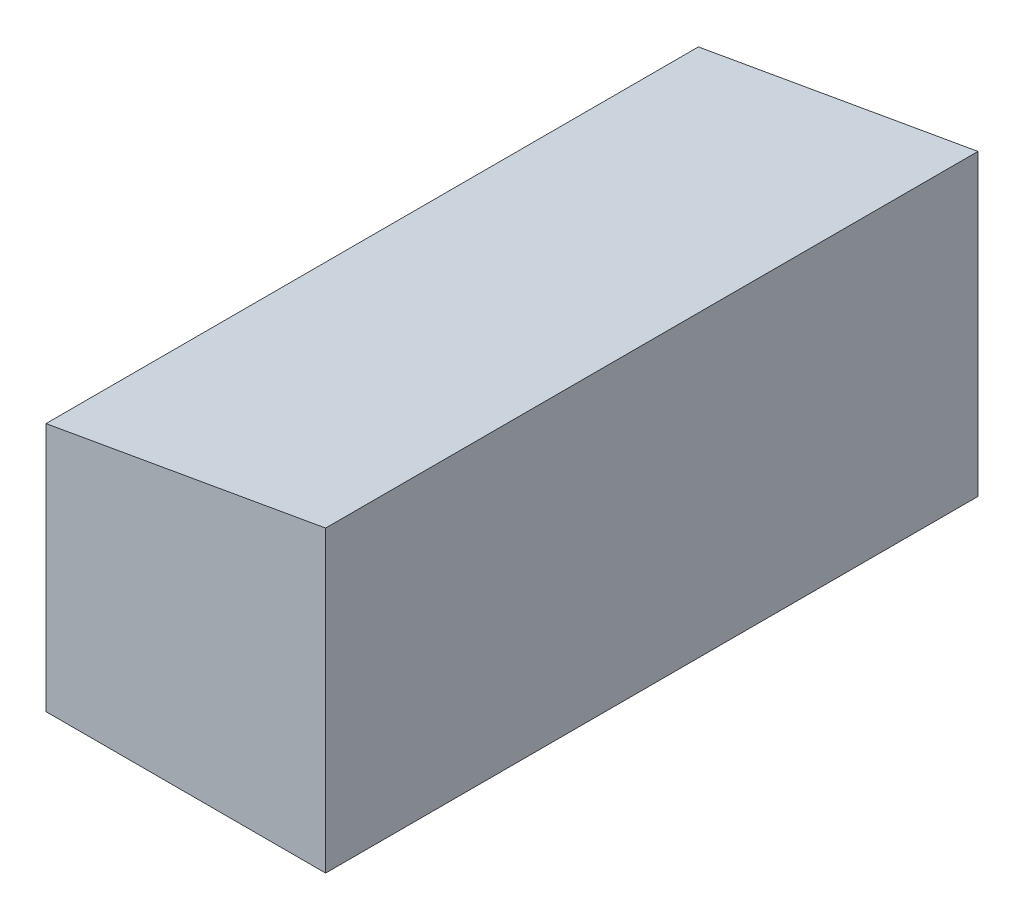
SolidWorks part; units mm, degrees
material "SPF Select 2Btr Grade Lumber"
ref_plane "Front Plane" through (0, 0, 0) normal (0, 0, 1) x (1, 0, 0)
ref_plane "Top Plane" through (0, 0, 0) normal (0, 1, 0) x (1, 0, 0)
ref_plane "Right Plane" through (0, 0, 0) normal (1, 0, 0) x (0, 0, -1)
sketch "Sketch1" plane through (0, 0, 0) normal (0, 0, 1) x (1, 0, 0)
  line L0 (38.1, 40.7181) -> (0, 34)
  line L1 (0, 0) -> (38.1, 0)
  line L2 (0, 0) -> (0, 34)
  line L4 (38.1, 0) -> (38.1, 40.7181)
  dimension "D1" = 38.1
  dimension "D2" = 80
  dimension "D3" = 34
extrude "Boss-Extrude1" add sketch "Sketch1" along normal blind 88.9
